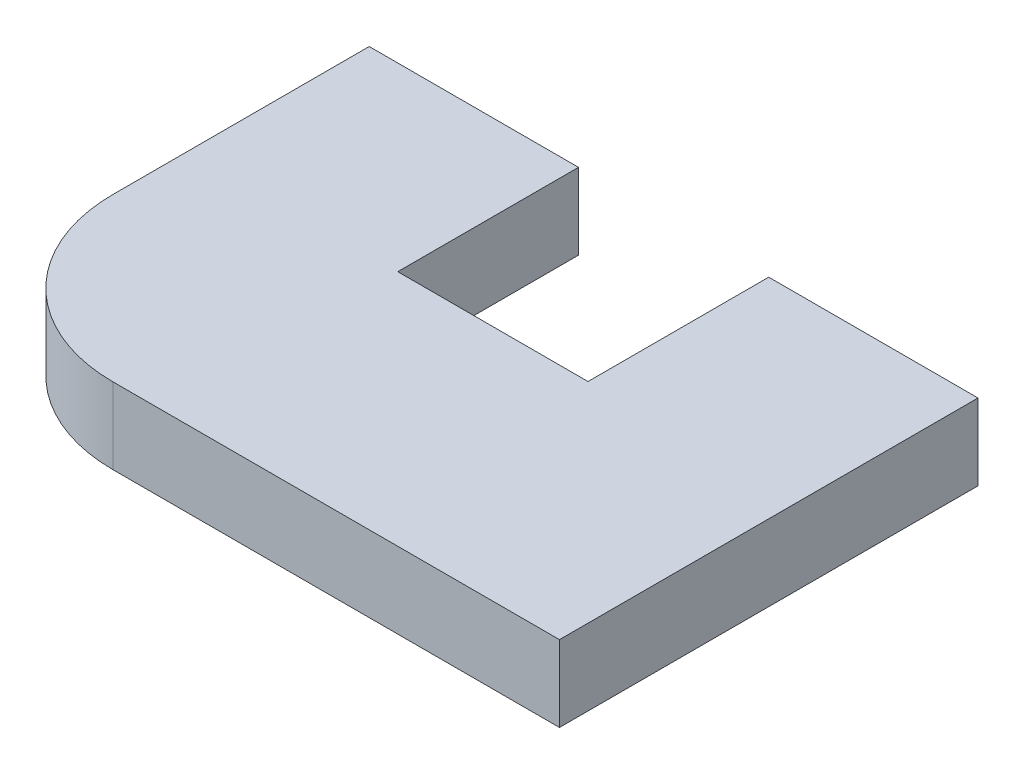
SolidWorks part; units mm, degrees
material "Ti-6Al-4VSolution treated and aged (SS)"
ref_plane "Front Plane" through (0, 0, 0) normal (0, 0, 1) x (1, 0, 0)
ref_plane "Top Plane" through (0, 0, 0) normal (0, 1, 0) x (1, 0, 0)
ref_plane "Right Plane" through (0, 0, 0) normal (1, 0, 0) x (0, 0, -1)
sketch "Sketch1" plane through (0, 0, 0) normal (0, 1, 0) x (1, 0, 0)
  line L1 (30.3553, -110) -> (55, -110)
  line L2 (-55, -24.6447) -> (-55, 110)
  line L3 (-55, 110) -> (55, 110)
  line L4 (55, -110) -> (55, 110)
  line L5 (-55, -110) -> (55, 110) construction
  line L6 (-55, 110) -> (55, -110) construction
  line L7 (55, -110) -> (155, -110)
  line L8 (55, -110) -> (55, 15)
  line L9 (55, 15) -> (155, 15)
  line L10 (155, -110) -> (155, 15)
  line L11 (155, -110) -> (265, -110)
  line L12 (155, -110) -> (155, 110)
  line L13 (155, 110) -> (265, 110)
  line L14 (265, -110) -> (265, 110)
  line L15 (-55, -110) -> (-30, -110) construction
  line L16 (-55, -110) -> (-55, -85) construction
  line L17 (-55, -85) -> (-30, -85) construction
  line L18 (-30, -110) -> (-30, -85) construction
  arc A0 (30.3553, -110) -> (-55, -24.6447) centre (30.3553, -24.6447) cw
  point P0 (0, 0)
  dimension "D1" = 25
  dimension "D2" = 220
  dimension "D3" = 100
  dimension "D4" = 125
  dimension "D5" = 210
  dimension "D6" = 25
extrude "Boss-Extrude1" add sketch "Sketch1" along normal blind 40 contours L1 L4 L3 L2 | L7 L10 L9 L4 | L11 L14 L13 L12 L10 region at (2.482, 0, -6.2808) region at (105, 0, 47.5) region at (210, 0, 0)
fillet "Fillet1" [suppressed] radius 10
fillet "Fillet2" [suppressed] radius 20
sketch "Sketch2" plane through (0, 0, 0) normal (0, 1, 0) x (1, 0, 0)
  line L0 (55, -110) -> (155, -110) construction
  line L2 (55, 15) -> (155, 15) construction
  line L4 (155, -110) -> (265, -110) construction
  line L5 (265, -110) -> (265, 110) construction
  line L6 (155, 110) -> (265, 110) construction
  line L7 (155, -110) -> (155, 110) construction
  line L8 (55, -110) -> (55, 110) construction
  line L9 (-55, 110) -> (55, 110) construction
  line L10 (-55, -24.6447) -> (-55, 110) construction
  line L11 (30.3553, -110) -> (55, -110) construction
  line L12 (55, -110) -> (155, -110)
  line L14 (55, 15) -> (155, 15)
  line L16 (155, -110) -> (265, -110)
  line L17 (265, -110) -> (265, 110)
  line L18 (155, 110) -> (265, 110)
  line L19 (155, 15) -> (155, 110)
  line L20 (55, 15) -> (55, 110)
  line L21 (-55, 110) -> (55, 110)
  line L22 (-55, -24.6447) -> (-55, 110)
  line L23 (30.3553, -110) -> (55, -110)
  arc A0 (-55, -24.6447) -> (30.3553, -110) centre (30.3553, -24.6447) ccw construction
  arc A1 (-55, -24.6447) -> (30.3553, -110) centre (30.3553, -24.6447) ccw
extrude "Boss-Extrude2" [suppressed] add sketch "Sketch2" along normal up to surface (40 mm away) separate body up to face at (94.742, 40, -23.0753)
shell "Shell4" [suppressed] thickness 2.54
shell "Shell5" [suppressed] thickness 2.54
